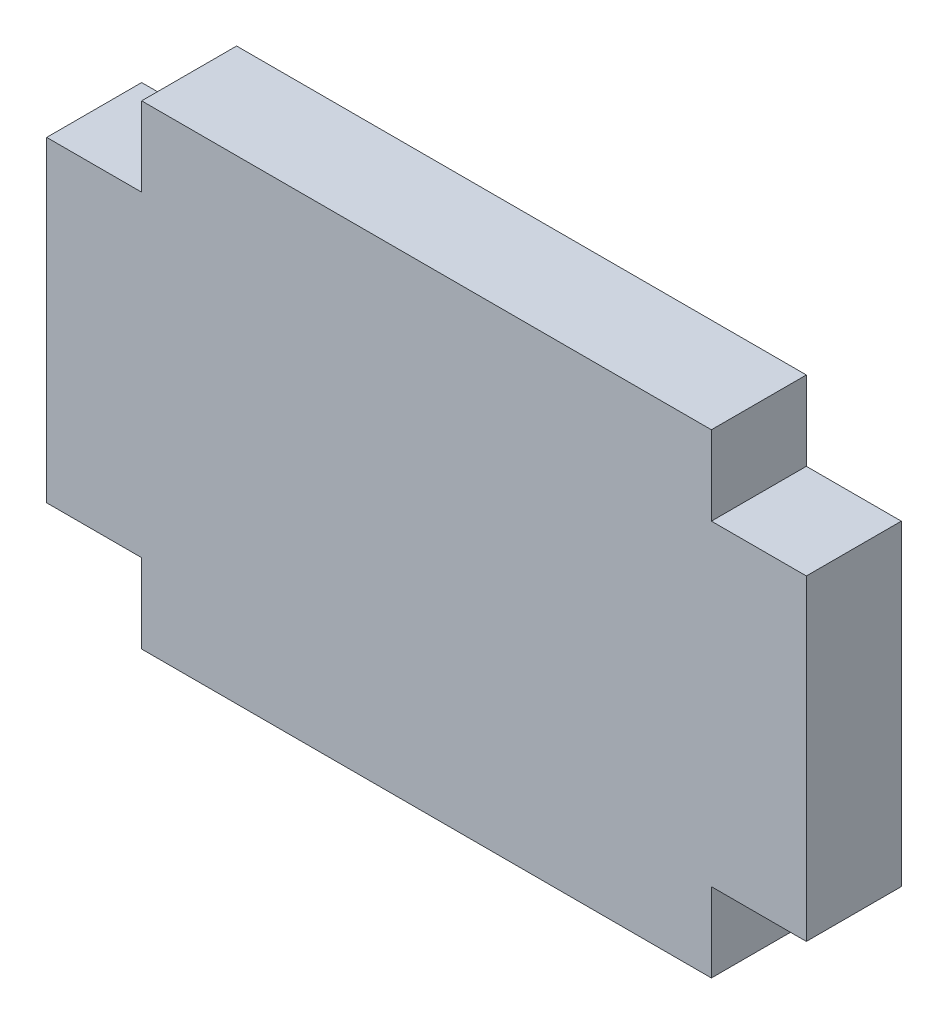
SolidWorks part; units mm, degrees
ref_plane "Plano frontal" through (0, 0, 0) normal (0, 0, 1) x (1, 0, 0)
ref_plane "Plano superior" through (0, 0, 0) normal (0, 1, 0) x (1, 0, 0)
ref_plane "Plano direito" through (0, 0, 0) normal (1, 0, 0) x (0, 0, -1)
sketch "Esboço1" plane through (0, 0, 0) normal (0, 0, 1) x (1, 0, 0)
  line L0 (0, 0) -> (9, 0) construction
  line L1 (-9, -7.5) -> (9, -7.5)
  line L2 (-9, -7.5) -> (-9, 7.5)
  line L3 (-9, 7.5) -> (9, 7.5)
  line L4 (9, -7.5) -> (9, 7.5)
  line L5 (-9, -7.5) -> (9, 7.5) construction
  line L6 (-9, 7.5) -> (9, -7.5) construction
  line L11 (0, 0) -> (0, -7.5) construction
  line L12 (-12, -5) -> (-9, -5)
  line L17 (-12, -5) -> (-12, 5)
  line L18 (-12, 5) -> (-9, 5)
  line L19 (-9, -5) -> (-9, 5)
  line L20 (-12, -5) -> (-9, 5) construction
  line L21 (-12, 5) -> (-9, -5) construction
  line L26 (12, 5) -> (9, 5)
  line L27 (9, -5) -> (9, 5)
  line L28 (12, -5) -> (9, -5)
  line L29 (12, -5) -> (12, 5)
  point P0 (0, 0)
  point P6 (-10.5, 0)
  dimension "D1" = 15
  dimension "D2" = 3
  dimension "D3" = 10
  dimension "D4" = 18
extrude "Ressalto-extrusão1" add sketch "Esboço1" along normal blind 3 contours L18 L17 L12 L2 | L28 L4 L3 L2 L1 | L28 L29 L26 L4 | L17 L12 L19 L18 region at (0, 0, 0) region at (-10.5, 0, 0) region at (10.5, 0, 0)
